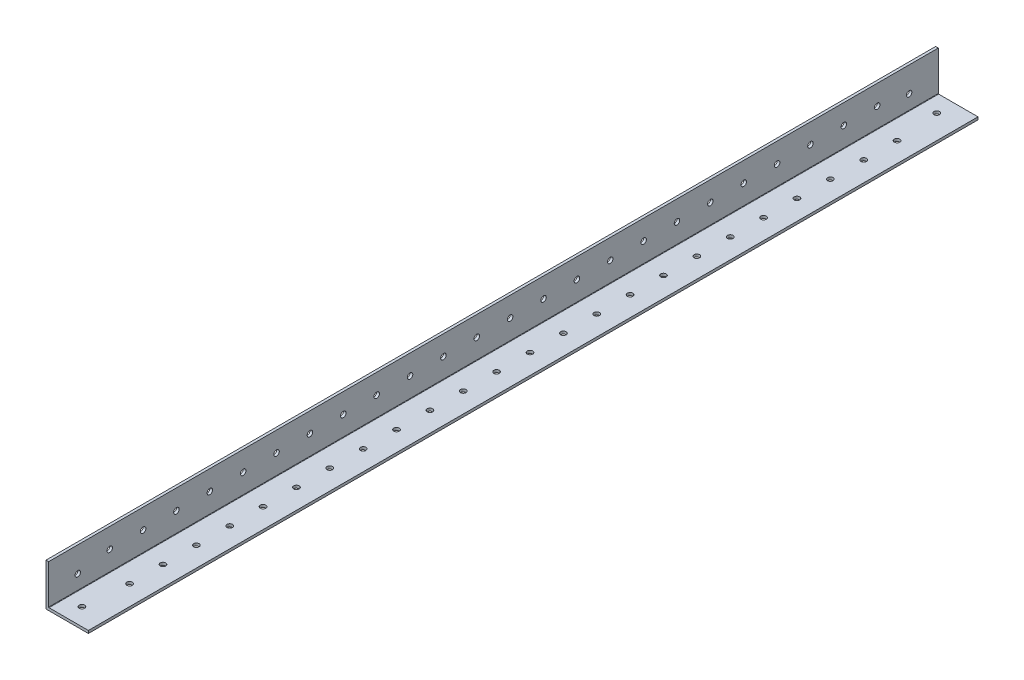
SolidWorks part; units mm, degrees
ref_plane "Front Plane" through (0, 0, 0) normal (0, 0, 1) x (1, 0, 0)
ref_plane "Top Plane" through (0, 0, 0) normal (0, 1, 0) x (1, 0, 0)
ref_plane "Right Plane" through (0, 0, 0) normal (1, 0, 0) x (0, 0, -1)
sketch "Sketch1" plane through (0, 0, 0) normal (0, 0, 1) x (1, 0, 0)
  line L0 (0, 25.4) -> (0, 0) construction
  line L1 (0, 0) -> (25.4, 0) construction
  line L2 (25.4, 0) -> (25.4, 1.5875) construction
  line L3 (25.4, 1.5875) -> (1.5875, 1.5875) construction
  line L4 (1.5875, 1.5875) -> (1.5875, 25.4) construction
  line L6 (1.5875, 25.4) -> (0, 25.4) construction
  arc A0 (1.5875, 1.8415) -> (1.8415, 1.5875) centre (1.8415, 1.8415) ccw construction
  point P4 (0, 0)
  dimension "Inside Corner Radius" = 0.254
  dimension "Outside Height" = 25.4
  dimension "Inside Height" = 23.8125
  dimension "Outside Width" = 25.4
  dimension "Inside Width" = 23.8125
  dimension "Wall Thickness" = 1.5875
  dimension "Shape" = 90
sketch "Sketch2" plane through (0, 0, 0) normal (1, 0, 0) x (0, 0, -1)
  line L0 (1219.2, 0) -> (-1219.2, 0) construction
  line L1 (-1219.2, 25.4) -> (-1219.2, 0) construction
  line L2 (1219.2, 25.4) -> (1219.2, 0) construction
  point P0 (-1189.99, 0)
  point P4 (0, 0)
  point P6 (1189.99, 0)
  dimension "D1" = 29.21
  dimension "D2" = 29.21
  dimension "D3" = 25.4
  dimension "Length" = 2438.4
sketch "Sketch3" plane through (0, 0, 0) normal (0, 0, 1) x (1, 0, 0)
  line L0 (1.5875, 25.4) -> (0, 25.4)
  line L1 (0, 25.4) -> (0, 0)
  line L2 (0, 0) -> (25.4, 0)
  line L3 (25.4, 0) -> (25.4, 1.5875)
  line L4 (25.4, 1.5875) -> (1.5875, 1.5875)
  line L5 (1.5875, 1.5875) -> (1.5875, 25.4)
extrude "Boss-Extrude1" add sketch "Sketch3" along normal mid plane 2438.4
fillet "Fillet1" radius 0.254 1 edges at (1.5875, 1.5875, 0)
sketch "Sketch4" plane through (0, 0, 0) normal (-1, 0, 0) x (0, 0, 1)
  line L0 (1219.2, 25.4) -> (1219.2, 0) construction
  line L1 (-1219.2, 0) -> (686, 0)
  line L2 (-1219.2, 0) -> (-1219.2, 74.9453)
  line L3 (-1219.2, 74.9453) -> (686, 74.9453)
  line L4 (686, 0) -> (686, 74.9453)
  dimension "D1" = 533.2
extrude "Cut-Extrude1" cut sketch "Sketch4" against normal blind 60
sketch "Sketch9" plane through (1.5875, 0, 0) normal (1, 0, 0) x (0, 0, -1)
  line L0 (-722.6, 1.5875) -> (-722.6, 25.4) construction
  line L1 (-1219.2, 1.5875) -> (-686, 1.5875) construction
  line L2 (-1219.2, 25.4) -> (-686, 25.4) construction
  line L3 (-703.4625, 10.3759) -> (-722.6, 10.3759) construction
  line L4 (-1182.6, 25.4) -> (-1182.6, 1.5875) construction
  line L5 (-1201.7375, 10.3759) -> (-1182.6, 10.3759) construction
  circle A0 centre (-1201.7375, 10.3759) radius 1.65
  circle A1 centre (-703.4625, 10.3759) radius 1.65
  circle A2 centre (-722.6, 13.4937) radius 1.65
  circle A3 centre (-742.6, 13.4937) radius 1.65
  circle A4 centre (-762.6, 13.4937) radius 1.65
  circle A5 centre (-782.6, 13.4937) radius 1.65
  circle A6 centre (-802.6, 13.4937) radius 1.65
  circle A7 centre (-822.6, 13.4937) radius 1.65
  circle A8 centre (-842.6, 13.4937) radius 1.65
  circle A9 centre (-862.6, 13.4937) radius 1.65
  circle A10 centre (-882.6, 13.4937) radius 1.65
  circle A11 centre (-902.6, 13.4937) radius 1.65
  circle A12 centre (-922.6, 13.4937) radius 1.65
  circle A13 centre (-942.6, 13.4937) radius 1.65
  circle A14 centre (-962.6, 13.4937) radius 1.65
  circle A15 centre (-982.6, 13.4937) radius 1.65
  circle A16 centre (-1002.6, 13.4937) radius 1.65
  circle A17 centre (-1022.6, 13.4937) radius 1.65
  circle A18 centre (-1042.6, 13.4937) radius 1.65
  circle A19 centre (-1062.6, 13.4937) radius 1.65
  circle A20 centre (-1082.6, 13.4937) radius 1.65
  circle A21 centre (-1102.6, 13.4937) radius 1.65
  circle A22 centre (-1122.6, 13.4937) radius 1.65
  circle A23 centre (-1142.6, 13.4937) radius 1.65
  circle A24 centre (-1162.6, 13.4937) radius 1.65
  circle A25 centre (-1182.6, 13.4937) radius 1.65
  dimension "D1" = 3.3
  dimension "D2" = 20
extrude "Cut-Extrude5" cut sketch "Sketch9" against normal blind 60
sketch "Sketch10" plane through (0, 1.5875, 0) normal (0, 1, 0) x (1, 0, 0)
  line L0 (25.4, -1182.6) -> (1.5875, -1182.6) construction
  line L1 (25.4, -1219.2) -> (25.4, -686) construction
  line L2 (1.5875, -1219.2) -> (1.5875, -686) construction
  line L3 (11.1125, -1208.7918) -> (11.1125, -1182.6) construction
  line L4 (11.1125, -696.4082) -> (25.4, -696.4082) construction
  line L5 (13.4937, -722.6) -> (13.4937, -696.4082) construction
  circle A0 centre (11.1125, -696.4082) radius 1.65
  circle A1 centre (11.1125, -1208.7918) radius 1.65
  circle A2 centre (13.4938, -1182.6) radius 1.65
  circle A3 centre (13.4938, -1162.6) radius 1.65
  circle A4 centre (13.4938, -1142.6) radius 1.65
  circle A5 centre (13.4938, -1122.6) radius 1.65
  circle A6 centre (13.4938, -1102.6) radius 1.65
  circle A7 centre (13.4938, -1082.6) radius 1.65
  circle A8 centre (13.4938, -1062.6) radius 1.65
  circle A9 centre (13.4938, -1042.6) radius 1.65
  circle A10 centre (13.4938, -1022.6) radius 1.65
  circle A11 centre (13.4938, -1002.6) radius 1.65
  circle A12 centre (13.4938, -982.6) radius 1.65
  circle A13 centre (13.4938, -962.6) radius 1.65
  circle A14 centre (13.4938, -942.6) radius 1.65
  circle A15 centre (13.4938, -922.6) radius 1.65
  circle A16 centre (13.4938, -902.6) radius 1.65
  circle A17 centre (13.4938, -882.6) radius 1.65
  circle A18 centre (13.4938, -862.6) radius 1.65
  circle A19 centre (13.4938, -842.6) radius 1.65
  circle A20 centre (13.4938, -822.6) radius 1.65
  circle A21 centre (13.4938, -802.6) radius 1.65
  circle A22 centre (13.4938, -782.6) radius 1.65
  circle A23 centre (13.4938, -762.6) radius 1.65
  circle A24 centre (13.4938, -742.6) radius 1.65
  circle A25 centre (13.4937, -722.6) radius 1.65
  dimension "D1" = 3.3
  dimension "D3" = 20
  dimension "D2" = 24
extrude "Cut-Extrude6" cut sketch "Sketch10" against normal blind 60
equation "\"D1@Boss-Extrude1\"=\"Length@Sketch2\""
equation "\"D1@Sketch2\" = \"Outside Width@Sketch1\" * 1.15"
equation "\"D2@Sketch2\"=\"D1@Sketch2\""
equation "\"D1@Fillet1\"=\"Inside Corner Radius@Sketch1\""
equation "\"D3@Sketch2\"=\"Outside Height@Sketch1\""
